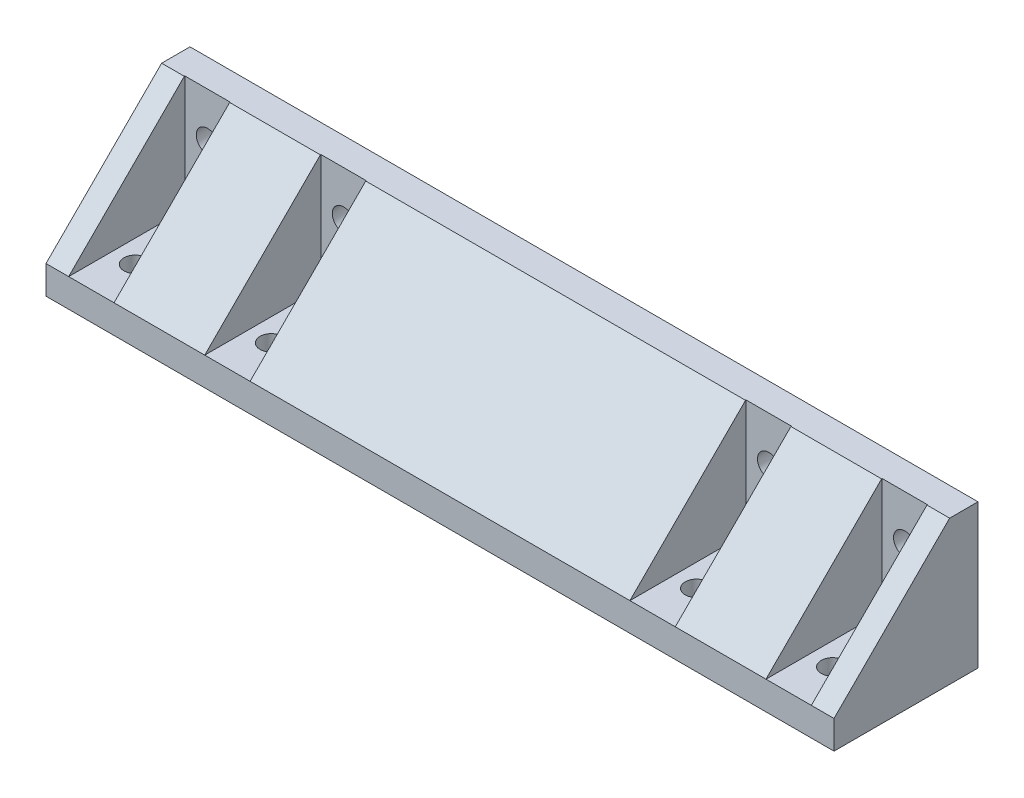
SolidWorks part; units mm, degrees
ref_plane "Front" through (0, 0, 0) normal (0, 0, 1) x (1, 0, 0)
ref_plane "Top" through (0, 0, 0) normal (0, 1, 0) x (1, 0, 0)
ref_plane "Right" through (0, 0, 0) normal (1, 0, 0) x (0, 0, -1)
sketch "Sketch1" plane through (0, 0, 0) normal (0, 1, 0) x (1, 0, 0)
  line L0 (0, 25.4) -> (0, 31.75)
  line L1 (0, 0) -> (139, 0)
  line L2 (0, 0) -> (0, 25.4)
  line L3 (0, 25.4) -> (139, 25.4)
  line L4 (139, 0) -> (139, 25.4)
  line L5 (0, 31.75) -> (0, 23.75)
  line L6 (0, 23.75) -> (0, 15.75)
  line L7 (0, 15.75) -> (0, 7.75)
  line L8 (0, 7.75) -> (0, -0.25)
  line L9 (0, 15.75) -> (139, 15.75)
  line L10 (0, 7.75) -> (139, 7.75)
  line L11 (0, 15.75) -> (8, 15.75)
  line L12 (8, 15.75) -> (16, 15.75)
  line L13 (16, 15.75) -> (24, 15.75)
  line L14 (24, 15.75) -> (32, 15.75)
  line L15 (32, 15.75) -> (107, 15.75)
  line L16 (107, 15.75) -> (131, 15.75)
  line L17 (0, 25.4) -> (0, 20.4)
  line L18 (0, 20.4) -> (139, 20.4)
  circle A0 centre (8, 15.75) radius 2
  circle A3 centre (32, 15.75) radius 2
  circle A5 centre (32, 7.75) radius 2
  circle A6 centre (8, 7.75) radius 2
  circle A7 centre (107, 15.75) radius 2
  circle A8 centre (131, 15.75) radius 2
  circle A9 centre (107, 7.75) radius 2
  circle A10 centre (131, 7.75) radius 2
  dimension "D12" = 8
  dimension "D14" = 5
  dimension "D1" = 139
  dimension "D2" = 6.35
  dimension "D3" = 8
  dimension "D4" = 8
  dimension "D5" = 8
  dimension "D6" = 8
  dimension "D7" = 25.4
  dimension "D8" = 8
  dimension "D9" = 8
  dimension "D10" = 8
  dimension "D11" = 8
  dimension "D13" = 24
  dimension "D15" = 8
  dimension "D16" = 8
extrude "Boss-Extrude1" add sketch "Sketch1" along normal blind 5 contours A10 L10 L4 L9 A8 L16 A7 L15 A3 L12 A0 L2 A6 A5 A9 | A10 L10 A9 A5 A6 L2 L1 L4 | A8 L9 L4 L18 L2 A0 L12 A3 L15 A7 L16 | L6 L18 L4 L3 L2 region at (69.5, 0, -3.8027) region at (69.5, 0, -11.75) region at (69.5, 0, -18.1347) region at (69.5, 0, -22.9)
sketch "Sketch3" plane through (0, 5, 0) normal (0, 1, 0) x (1, 0, 0)
  line L0 (0, 25.4) -> (139, 25.4)
  line L1 (0, 25.4) -> (0, 20.4)
  line L2 (139, 25.4) -> (139, 20.4)
  line L3 (0, 20.4) -> (139, 20.4)
  dimension "D1" = 5
extrude "Boss-Extrude2" add sketch "Sketch3" along normal blind 20.4
sketch "Sketch4" plane through (0, 5, 0) normal (0, 1, 0) x (1, 0, 0)
  line L1 (0, 20.4) -> (139, 20.4)
  line L2 (0, 20.4) -> (0, 0)
  line L3 (0, 0) -> (139, 0)
  line L4 (139, 20.4) -> (139, 0)
extrude "Boss-Extrude3" add sketch "Sketch4" along normal blind 20.5
sketch "Sketch5" plane through (139, 0, 0) normal (1, 0, 0) x (0, 0, -1)
  line L0 (20.4, 25.4) -> (0, 5)
  line L1 (0, 25.5) -> (0, 0) construction
  line M4 (20.4, 25.4) -> (20.4, 25.5)
  line M5 (20.4, 25.5) -> (0, 25.5)
  line M6 (0, 25.5) -> (0, 0)
  dimension "D1" = 5
extrude "Cut-Extrude1" cut sketch "Sketch5" against normal through all and the other way through all contours L0 M4 M5 M6 region at (139, 18.6665, -6.833)
sketch "Sketch7" plane through (0, 0, 0) normal (0, 0, 1) x (1, 0, 0)
  line L0 (0, 0) -> (139, 0) construction
  line L1 (4, 0) -> (12, 0)
  line L2 (4, 0) -> (4, 25.4)
  line L3 (4, 25.4) -> (12, 25.4)
  line L4 (12, 0) -> (12, 25.4)
  line L5 (0, 5) -> (139, 5)
  line L6 (28, 0) -> (36, 0)
  line L7 (28, 0) -> (28, 25.4)
  line L8 (28, 25.4) -> (36, 25.4)
  line L9 (36, 0) -> (36, 25.4)
  line L10 (103, 0) -> (111, 0)
  line L11 (103, 0) -> (103, 25.4)
  line L12 (103, 25.4) -> (111, 25.4)
  line L13 (111, 0) -> (111, 25.4)
  line L14 (127, 0) -> (135, 0)
  line L15 (127, 0) -> (127, 25.4)
  line L16 (127, 25.4) -> (135, 25.4)
  line L17 (135, 0) -> (135, 25.4)
  line L18 (139, 5) -> (139, 0) construction
  line M10 (139, 5) -> (0, 5)
  dimension "D1" = 25.4
  dimension "D2" = 25.4
  dimension "D3" = 25.4
  dimension "D4" = 25.4
  dimension "D5" = 4
  dimension "D6" = 8
  dimension "D7" = 16
  dimension "D8" = 8
  dimension "D9" = 8
  dimension "D10" = 8
  dimension "D11" = 4
  dimension "D12" = 16
extrude "Cut-Extrude2" cut sketch "Sketch7" against normal blind 20.5 contours L4 L3 L2 M10 | L5 L9 L8 L7 | L5 L13 L12 L11 | L5 L17 L16 L15 region at (131, 15.2, 0) region at (107, 15.2, 0) region at (32, 15.2, 0) region at (8, 15.2, 0)
sketch "Sketch8" plane through (0, 0, -20.5) normal (0, 0, 1) x (1, 0, 0)
  line L0 (131, 25.4) -> (131, 17.4)
  line L1 (127, 25.4) -> (135, 25.4) construction
  line L2 (107, 25.4) -> (107, 17.4)
  line L3 (103, 25.4) -> (111, 25.4) construction
  line L4 (32, 25.4) -> (32, 17.4)
  line L5 (28, 25.4) -> (36, 25.4) construction
  line L6 (8, 25.4) -> (8, 17.4)
  line L7 (4, 25.4) -> (12, 25.4) construction
  circle A0 centre (8, 17.4) radius 2
  circle A1 centre (32, 17.4) radius 2
  circle A2 centre (107, 17.4) radius 2
  circle A3 centre (131, 17.4) radius 2
  dimension "D1" = 8
extrude "Cut-Extrude3" cut sketch "Sketch8" against normal blind 10 contours A3 | A0 | A1 | A2 region at (129.6258, 16.0258, -20.5)
